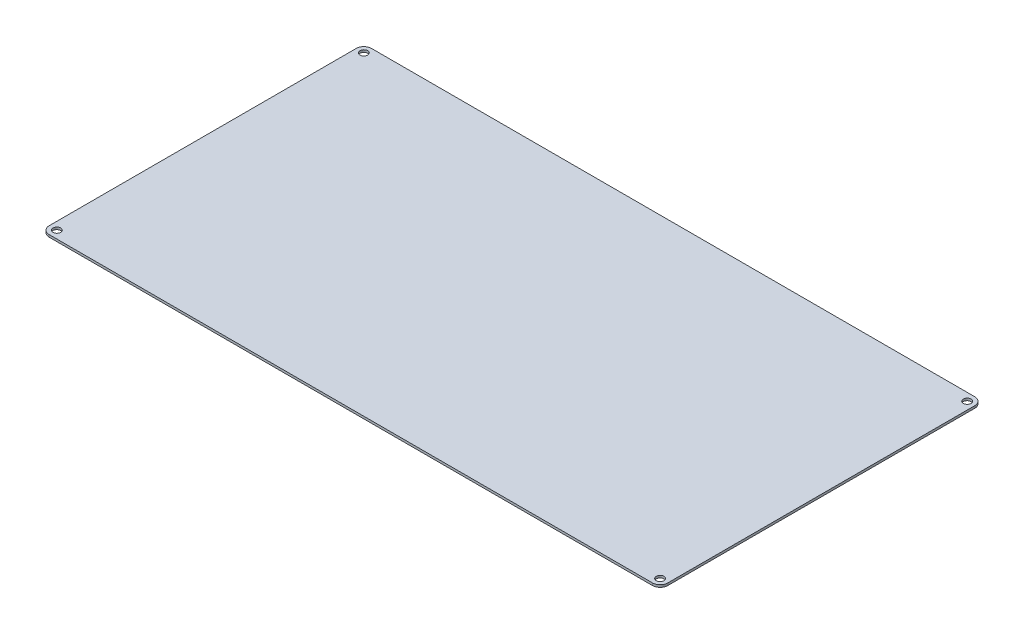
SolidWorks part; units mm, degrees
note: The reader was unsure of these and kept them because the rebuilt part matched: thickness of "Base-Flange1", "Sheet-Metal1".
material "Galvanized Steel"
ref_plane "Front" through (0, 0, 0) normal (0, 0, 1) x (1, 0, 0)
ref_plane "Top" through (0, 0, 0) normal (0, 1, 0) x (1, 0, 0)
ref_plane "Right" through (0, 0, 0) normal (1, 0, 0) x (0, 0, -1)
sketch "Sketch1" plane through (0, 0, 0) normal (0, 1, 0) x (1, 0, 0)
  line L1 (5, 0) -> (398, 0)
  line L2 (0, 5) -> (0, 205)
  line L3 (5, 210) -> (398, 210)
  line L4 (403, 5) -> (403, 205)
  arc A0 (403, 5) -> (398, 0) centre (398, 5) cw
  arc A1 (5, 0) -> (0, 5) centre (5, 5) cw
  arc A2 (5, 210) -> (0, 205) centre (5, 205) ccw
  arc A6 (403, 205) -> (398, 210) centre (398, 205) ccw
  circle A9 centre (5, 205) radius 2.5
  circle A10 centre (5, 5) radius 2.5
  circle A11 centre (398, 5) radius 2.5
  circle A12 centre (398, 205) radius 2.5
  point P9 (0, 0)
  point P12 (0, 210)
  point P15 (403, 210)
  dimension "D3" = 5
  dimension "D1" = 5
  dimension "D4" = 210
  dimension "D2" = 403
base flange "Base-Flange1" sketch "Sketch1" thickness 1.5 reverse thickness direction no parameters "D1"=2
sketch "Bend-Lines1" [suppressed] plane through (0, 0, 0) normal (0, 1, 0) x (1, 0, 0)
sketch "Bounding-Box1" [suppressed] plane through (0, 0, 0) normal (0, 1, 0) x (1, 0, 0)
sheet metal parameters "Sheet-Metal1" thickness 1.5 parameters "D1"=10, "D7"=1
flat pattern "Flat-Pattern1" [suppressed]
sketch "Bend-Lines2" plane through (0, 0, 0) normal (0, 1, 0) x (1, 0, 0)
sketch3d "Bounding-Box2" [suppressed]
  line L0 (-398, 204.9998, 0) -> (5, 205, 0) construction
  line L1 (-397.9999, -5, 0) -> (5.0001, -4.9998, 0) construction
  line L2 (-398, 204.9998, 0) -> (-397.9999, -5, 0) construction
  line L3 (5, 205, 0) -> (5.0001, -4.9998, 0) construction
